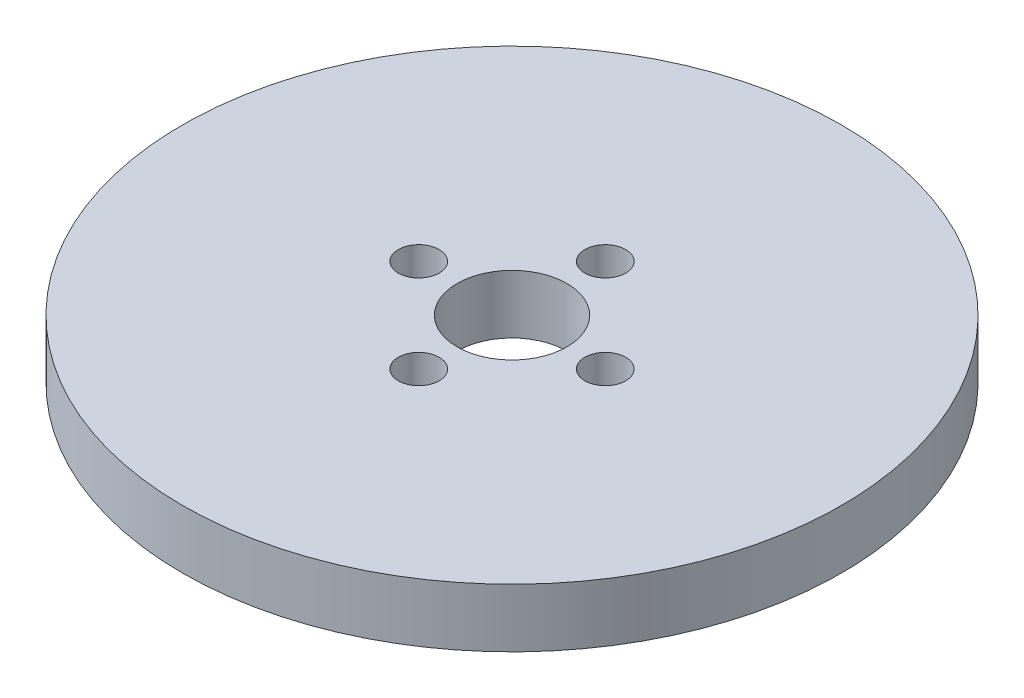
SolidWorks part; units mm, degrees
ref_plane "Front Plane" through (0, 0, 0) normal (0, 0, 1) x (1, 0, 0)
ref_plane "Top Plane" through (0, 0, 0) normal (0, 1, 0) x (1, 0, 0)
ref_plane "Right Plane" through (0, 0, 0) normal (1, 0, 0) x (0, 0, -1)
sketch "Sketch1" plane through (0, 0, 0) normal (0, 1, 0) x (1, 0, 0)
  circle A0 centre (0, 0) radius 45
  dimension "FLANGE_OD" = 90
extrude "Boss-Extrude1" add sketch "Sketch1" along normal blind 8
sketch "Sketch2" plane through (0, 0, 0) normal (0, 1, 0) x (1, 0, 0)
  circle A0 centre (0, 0) radius 7.5
  dimension "BORE_D" = 15
extrude "Cut-Extrude1" cut sketch "Sketch2" along normal through all
sketch "Sketch3" plane through (0, 8, 0) normal (0, 1, 0) x (1, 0, 0)
  circle A0 centre (0, 0) radius 12.7363 construction
  circle A1 centre (-12.7363, 0) radius 2.7898
  dimension "BOLT_D" = 5.5795
  dimension "BOLT_PCD" = 25.4725
extrude "Cut-Extrude2" cut sketch "Sketch3" against normal blind 5.0395
pattern_circular "CirPattern1" count 4 over 360 about axis through (0, 0, 0) along (0, 1, 0) of "Cut-Extrude2"
